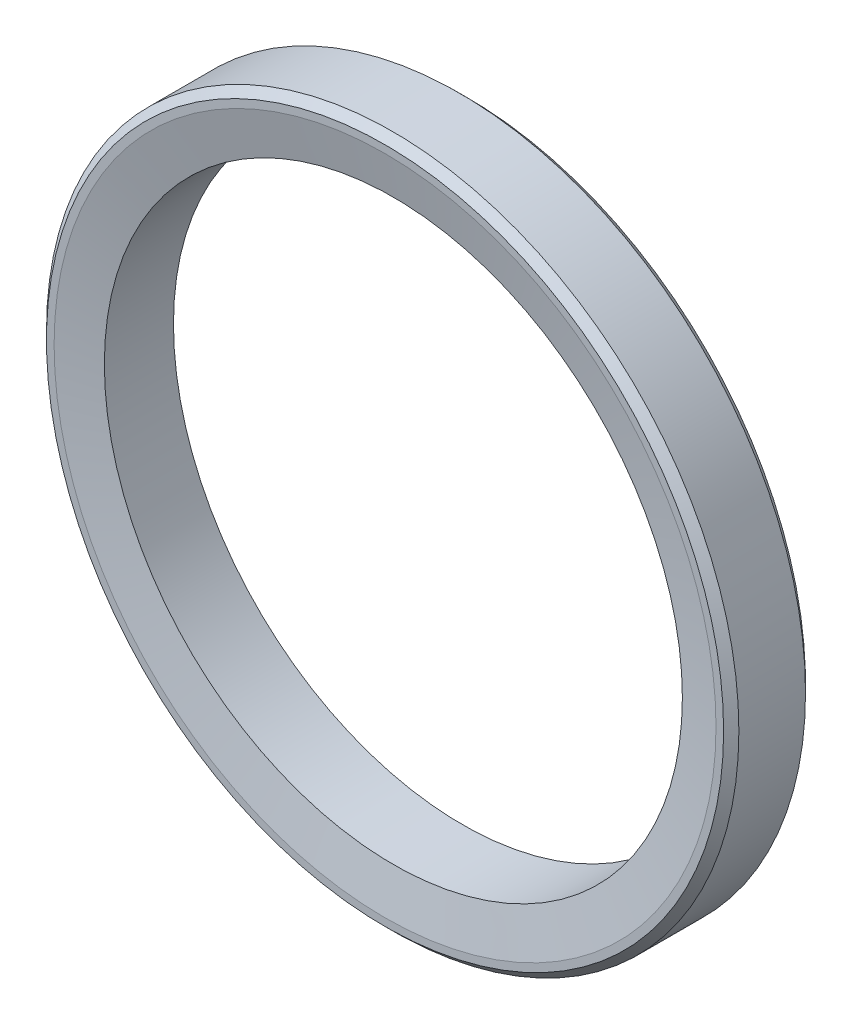
SolidWorks part; units mm, degrees
material "Brass"
ref_plane "Front Plane" through (0, 0, 0) normal (0, 0, 1) x (1, 0, 0)
ref_plane "Top Plane" through (0, 0, 0) normal (0, 1, 0) x (1, 0, 0)
ref_plane "Right Plane" through (0, 0, 0) normal (1, 0, 0) x (0, 0, -1)
sketch "Sketch2" plane through (0, 0, 0) normal (1, 0, 0) x (0, 0, -1)
  line L0 (-2.8105, 22.7) -> (2.5595, 22.7)
  line L1 (-2.8105, 22.7) -> (-2.8105, 21.7)
  line L2 (-2.2655, 18.95) -> (2.2655, 18.95)
  line L3 (2.5595, 22.7) -> (2.5595, 22.2)
  line L4 (2.5595, 22.2) -> (2.2655, 18.95)
  line L5 (-2.8105, 21.7) -> (-2.2655, 18.95)
  point P16 (0, 18.95)
  dimension "D4" = 11.21
  dimension "D6" = 5.17
  dimension "D1" = 1
  dimension "D2" = 0.5
  dimension "D3" = 3.75
  dimension "D5" = 22.7
  dimension "D7" = 5.37
ref_axis "Axis1" through (0, 0, -1.4088) along (0, 0, 1)
revolve "Revolve1" add sketch "Sketch2" angle 360 about axis through (0, 0, -1.4088) along (0, 0, 1)
chamfer "Chamfer1" distance 0.5 angle 45 2 edges at (-22.7, 0, -2.5595) (-22.7, 0, 2.8105)
